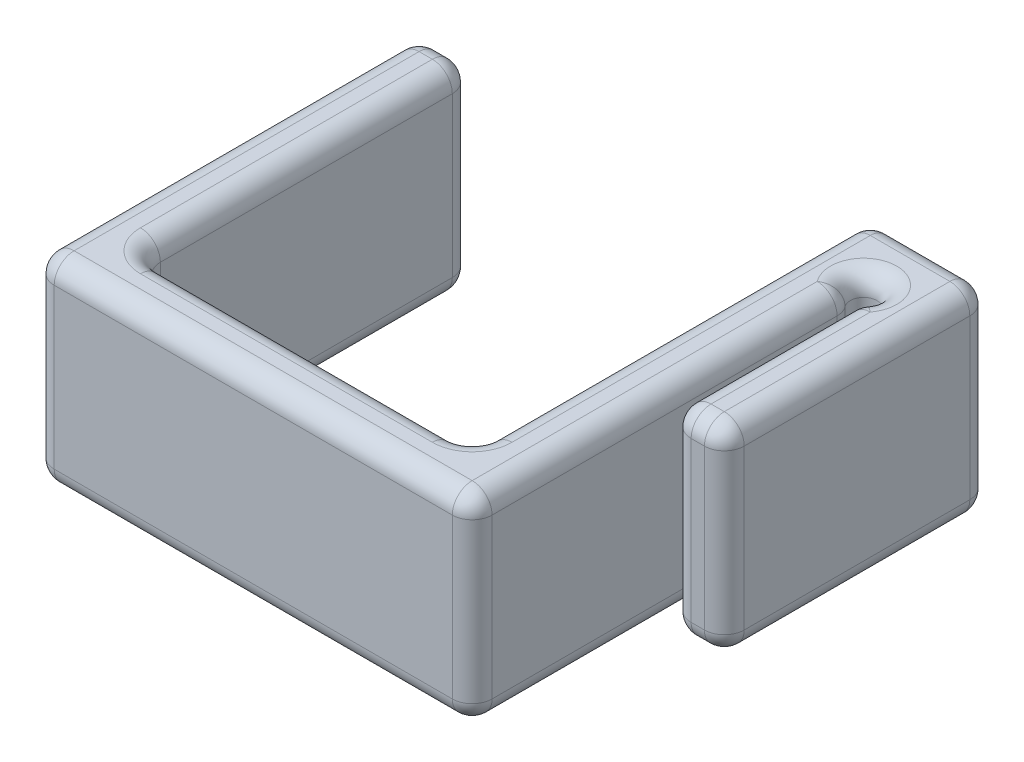
SolidWorks part; units mm, degrees
ref_plane "Front Plane" through (0, 0, 0) normal (0, 0, 1) x (1, 0, 0)
ref_plane "Top Plane" through (0, 0, 0) normal (0, 1, 0) x (1, 0, 0)
ref_plane "Right Plane" through (0, 0, 0) normal (1, 0, 0) x (0, 0, -1)
sketch "Sketch1" plane through (0, 0, 0) normal (0, 1, 0) x (1, 0, 0)
  line L0 (1.8165, 4.1812) -> (1.8165, -29.8188) construction
  line L1 (-2.6835, 4.1812) -> (6.3165, 4.1812)
  line L2 (-2.6835, 4.1812) -> (-2.6835, -29.8188)
  line L3 (-2.6835, -29.8188) -> (6.3165, -29.8188)
  line L4 (6.3165, 4.1812) -> (6.3165, -29.8188)
  line L5 (6.3165, -15.8188) -> (2.3165, -15.8188)
  line L6 (-2.6835, -29.8188) -> (-31.6835, -29.8188)
  line L7 (-2.6835, -29.8188) -> (-2.6835, -25.8188)
  line L8 (-2.6835, -25.8188) -> (-31.6835, -25.8188)
  line L9 (-31.6835, -29.8188) -> (-31.6835, -25.8188)
  line L10 (-31.6835, -25.8188) -> (-27.6835, -25.8188)
  line L11 (-31.6835, -25.8188) -> (-31.6835, -0.8188)
  line L12 (-31.6835, -0.8188) -> (-27.6835, -0.8188)
  line L13 (-27.6835, -25.8188) -> (-27.6835, -0.8188)
  line L14 (1.3165, -29.8188) -> (2.3165, -29.8188)
  line L15 (1.3165, -29.8188) -> (1.3165, -0.8188)
  line L16 (1.3165, -0.8188) -> (2.3165, -0.8188)
  line L17 (2.3165, -29.8188) -> (2.3165, -0.8188)
  circle A0 centre (1.8165, -0.8188) radius 1
  point P18 (1.8165, -0.8188)
  dimension "D3" = 2
  dimension "D1" = 9
  dimension "D2" = 25
  dimension "D4" = 5
  dimension "D5" = 4
  dimension "D6" = 4
  dimension "D7" = 25
  dimension "D8" = 25
  dimension "D9" = 1
  dimension "D10" = 0
  dimension "D11" = 15
extrude "Boss-Extrude1" add sketch "Sketch1" along normal blind 15 contours L8 L13 L12 L11 | L9 L6 L2 L8 | L0 L1 L2 L3 L15 A0 | L1 L0 A0 L17 L5 L4 region at (4.2742, 0, 5.6584) region at (-0.6584, 0, 12.6521) region at (-17.1835, 0, 27.8188) region at (-29.6835, 0, 13.3188)
fillet "Fillet1" radius 1.5 30 edges at (-2.6835, 0, 10.8188) (6.3165, 0, 5.8188) (4.3165, 0, 15.8188) (-15.1835, 0, 25.8188) (-15.1835, 0, 29.8188) (-31.6835, 0, 15.3188) (-27.6835, 0, 13.3188) (4.3165, 15, 15.8188) (6.3165, 15, 5.8188) (1.8165, 15, -4.1812) (-2.6835, 15, 10.8188) (-15.1835, 15, 25.8188) (-15.1835, 15, 29.8188) (-31.6835, 15, 15.3188) (-27.6835, 15, 13.3188) (1.3165, 7.5, 29.8188) (1.3165, 7.5, 1.6848) (2.3165, 7.5, 1.6848) (2.3165, 7.5, 15.8188) (6.3165, 7.5, 15.8188) (6.3165, 7.5, -4.1812) (-2.6835, 7.5, -4.1812) (-31.6835, 7.5, 29.8188) (-2.6835, 7.5, 25.8188) (-27.6835, 7.5, 25.8188) (-27.6835, 7.5, 0.8188) (-31.6835, 7.5, 0.8188) (1.8165, 0, -4.1812) (-29.6835, 0, 0.8188) (-29.6835, 15, 0.8188)
fillet "Fillet2" radius 1.5 14 edges at (0.8772, 0.4393, 29.3795) (2.7559, 0.4393, 15.3795) (2.3165, 0, 8.3188) (2.3935, 0, 1.8445) (1.8165, 0, -0.1812) (1.2395, 0, 1.8445) (0.8772, 14.5607, 29.3795) (2.7559, 14.5607, 15.3795) (2.3165, 15, 8.3188) (2.3935, 15, 1.8445) (1.8165, 15, -0.1812) (1.2395, 15, 1.8445) (1.3165, 0, 15.3188) (1.3165, 15, 15.3188)
